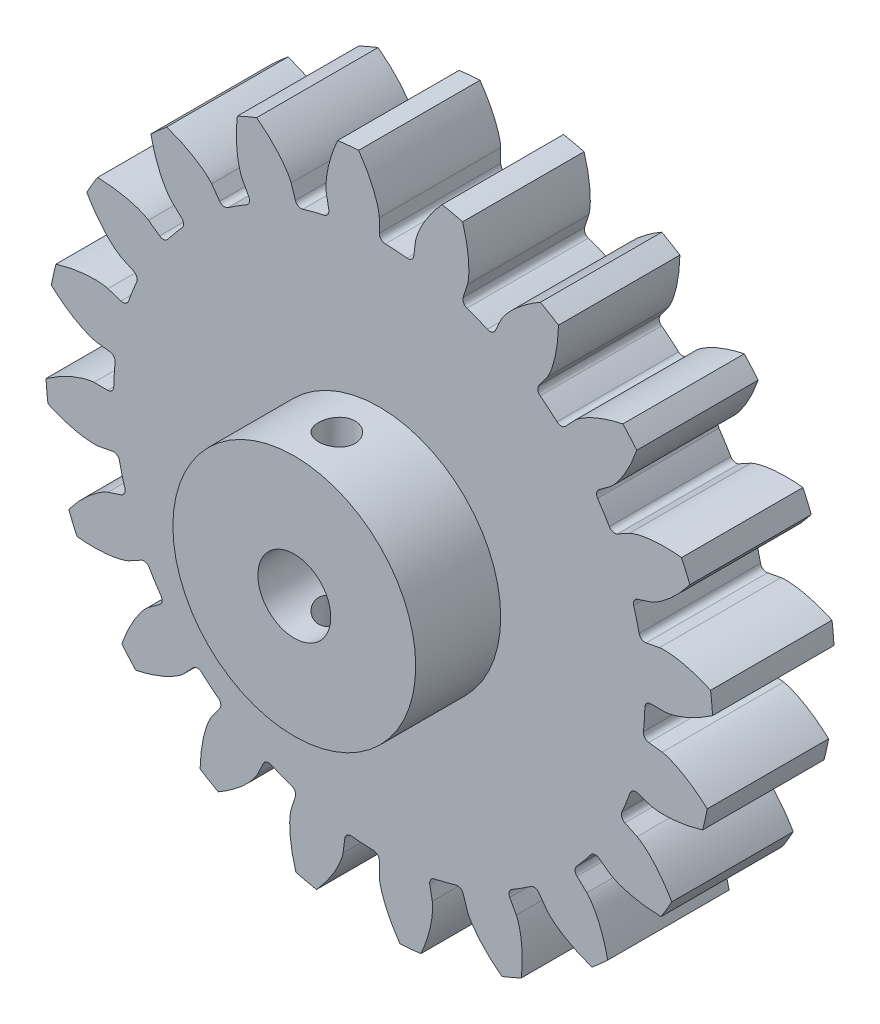
SolidWorks part; units mm, degrees
note: '?' marks a value the reader was unsure of.
material "Nylon 101"
ref_plane "Front Plane" through (0, 0, 0) normal (0, 0, 1) x (1, 0, 0)
ref_plane "Top Plane" through (0, 0, 0) normal (0, 1, 0) x (1, 0, 0)
ref_plane "Right Plane" through (0, 0, 0) normal (1, 0, 0) x (0, 0, -1)
sketch "Sketch1" plane through (0, 0, 0) normal (0, 0, 1) x (1, 0, 0)
  circle A0 centre (0, 0) radius 27.5
  dimension "D1" = 55
extrude "Boss-Extrude1" add sketch "Sketch1" along normal blind 10
sketch "Sketch2" plane through (0, 0, 10) normal (0, 0, 1) x (1, 0, 0)
  line L0 (22.3694, 0) -> (23.4923, 0)
  line L1 (0, 0) -> (27.4443, -1.7488) construction
  line L2 (22.1885, -2.8393) -> (23.3023, -2.9818)
  circle A0 centre (0, 0) radius 25 construction
  circle A1 centre (0, 0) radius 23.4923 construction
  arc A2 (21.7547, -2.291) -> (21.8695, -0.4888) centre (0, 0) ccw
  circle A3 centre (0, 0) radius 27.5 construction
  arc A4 (22.1885, -2.8393) -> (21.7547, -2.291) centre (22.252, -2.3433) cw
  arc A5 (21.8695, -0.4888) -> (22.3694, 0) centre (22.3694, -0.5) cw
  spline S0 degree 4 poles (23.4923, 0) (23.5003, 0.0001) (23.5229, 0.0008) (23.5654, 0.0035) (23.6347, 0.0099) (23.7229, 0.021) (23.8366, 0.0388) (23.9701, 0.064) (24.1163, 0.0963) (24.2747, 0.1362) (24.4321, 0.1804) (24.5885, 0.2284) (24.7436, 0.2799) (24.9307, 0.3464) (25.1538, 0.4321) (25.4127, 0.5406) (25.7039, 0.6737) (25.998, 0.82) (26.2849, 0.9725) (26.5718, 1.1365) (26.8473, 1.3021) (27.1301, 1.484) (27.3894, 1.6571) (27.6761, 1.8618) (27.9062, 2.0302) (28.2054, 2.2638) (28.3807, 2.4052) (28.5843, 2.5745) (28.6738, 2.6518) (28.729, 2.6993) knots 0 0 0 0 0 0.005377 0.015084 0.028532 0.04661 0.064855 0.092111 0.119476 0.146842 0.174209 0.201575 0.228941 0.256307 0.307035 0.361767 0.4165 0.471232 0.525964 0.580697 0.635429 0.690161 0.744894 0.799626 0.854358 0.909091 0.954545 1 1 1 1 1 construction
  spline S1 degree 4 poles (23.4923, 0) (23.5003, 0.0001) (23.5229, 0.0008) (23.5654, 0.0035) (23.6347, 0.0099) (23.7229, 0.021) (23.8366, 0.0388) (23.9701, 0.064) (24.1163, 0.0963) (24.2747, 0.1362) (24.4321, 0.1804) (24.5885, 0.2284) (24.7436, 0.2799) (24.9307, 0.3464) (25.1538, 0.4321) (25.4127, 0.5406) (25.7039, 0.6737) (25.998, 0.82) (26.2849, 0.9725) (26.5718, 1.1365) (26.8473, 1.3021) (27.1301, 1.484) (27.3894, 1.6571) (27.6761, 1.8618) (27.9062, 2.0302) (28.1405, 2.2132) (28.254, 2.3035) (28.3118, 2.3503) knots 0 0 0 0 0 0.005377 0.015084 0.028532 0.04661 0.064855 0.092111 0.119476 0.146842 0.174209 0.201575 0.228941 0.256307 0.307035 0.361767 0.4165 0.471232 0.525964 0.580697 0.635429 0.690161 0.744894 0.799626 0.854358 0.909091 0.909091 0.909091 0.909091 0.909091
  spline S2 degree 4 poles (23.3023, -2.9818) (23.3103, -2.983) (23.3325, -2.9865) (23.3744, -2.9946) (23.4423, -3.0097) (23.5284, -3.0319) (23.6389, -3.064) (23.7681, -3.106) (23.909, -3.1565) (24.0611, -3.2163) (24.2116, -3.2801) (24.3606, -3.3476) (24.5079, -3.4183) (24.6851, -3.508) (24.8955, -3.6213) (25.1385, -3.7618) (25.4105, -3.9308) (25.6836, -4.1132) (25.9489, -4.3009) (26.2126, -4.5) (26.4649, -4.6992) (26.7223, -4.9156) (26.9576, -5.1201) (27.2159, -5.3596) (27.4228, -5.5559) (27.6899, -5.8255) (27.8459, -5.988) (28.0263, -6.1818) (28.1053, -6.2699) (28.154, -6.324) knots 0 0 0 0 0 0.005377 0.015084 0.028532 0.04661 0.064855 0.092111 0.119476 0.146842 0.174209 0.201575 0.228941 0.256307 0.307035 0.361767 0.4165 0.471232 0.525964 0.580697 0.635429 0.690161 0.744894 0.799626 0.854358 0.909091 0.954545 1 1 1 1 1 construction
  spline S3 degree 4 poles (23.3023, -2.9818) (23.3103, -2.983) (23.3325, -2.9865) (23.3744, -2.9946) (23.4423, -3.0097) (23.5284, -3.0319) (23.6389, -3.064) (23.7681, -3.106) (23.909, -3.1565) (24.0611, -3.2163) (24.2116, -3.2801) (24.3606, -3.3476) (24.5079, -3.4183) (24.6851, -3.508) (24.8955, -3.6213) (25.1385, -3.7618) (25.4105, -3.9308) (25.6836, -4.1132) (25.9489, -4.3009) (26.2126, -4.5) (26.4649, -4.6992) (26.7223, -4.9156) (26.9576, -5.1201) (27.2159, -5.3596) (27.4228, -5.5559) (27.632, -5.7671) (27.7331, -5.8711) (27.7845, -5.9248) knots 0 0 0 0 0 0.005377 0.015084 0.028532 0.04661 0.064855 0.092111 0.119476 0.146842 0.174209 0.201575 0.228941 0.256307 0.307035 0.361767 0.4165 0.471232 0.525964 0.580697 0.635429 0.690161 0.744894 0.799626 0.854358 0.909091 0.909091 0.909091 0.909091 0.909091
  dimension "D1" = 50
  dimension "D2" = 46.9846
  dimension "D3" = 43.75
  dimension "D6" = 0.5
  dimension "D4" = 3.646
  dimension "D5" = 3.646
extrude "Cut-Extrude1" cut sketch "Sketch2" against normal through all and the other way through all
ref_axis "Axis2" through (0, 0, 10) along (0, 0, -1)?
pattern_circular "CirPattern6" count 20 over 360 about axis through (0, 0, 10) along (0, 0, -1) of "Cut-Extrude1"
sketch "Sketch3" plane through (0, 0, 10) normal (0, 0, 1) x (1, 0, 0)
  circle A0 centre (0, 0) radius 3
  circle A5 centre (0, 0) radius 7 construction
  dimension "D1" = 6
  dimension "D2" = 14
extrude "Cut-Extrude2" cut sketch "Sketch3" against normal blind 10
sketch "Sketch4" plane through (0, 0, 10) normal (0, 0, 1) x (1, 0, 0)
  circle A0 centre (0, 0) radius 3
  circle A1 centre (0, 0) radius 10
  circle A2 centre (0, 0) radius 3 construction
  dimension "D1" = 20
extrude "Boss-Extrude2" add sketch "Sketch4" along normal blind 7
ref_plane "Plane1" through (0, 0, 5) normal (0, 0, 1) x (1, 0, 0)
sketch "Sketch5" plane through (0, 0, 0) normal (0, 1, 0) x (1, 0, 0)
  line L0 (0, -10) -> (0, 0) construction
  line L1 (-23.4923, -10) -> (23.4923, -10) construction
  circle A0 centre (0, -13.5) radius 1.5
  dimension "D1" = 3
  dimension "D2" = 3.5
extrude "Cut-Extrude3" cut sketch "Sketch5" against normal through all and the other way through all
mirror "Mirror2" about plane through (0, 0, 5) normal (0, 0, 1) of "Boss-Extrude2", "Cut-Extrude3"
equation "\"m\"= 2.5'module"
equation "\"p\"= 1 / \"m\"'Diametral pitch"
equation "\"N\"= 20'Number of teeth"
equation "\"phi\"= 20'pressure angle"
equation "\"a\"= \"m\"'addendum"
equation "\"b\"= 1.25 * \"m\"'deddendum"
equation "\"c\"= \"b\" - \"a\"'clearance"
equation "\"dp\"= \"N\" * \"m\"'pitch circle diameter"
equation "\"db\"= \"dp\" * cos ( \"phi\" )'base circle diameter"
equation "\"D1@Sketch1\" = \"dp\" + 2 * \"a\"'Addendum circle dia "
equation "\"D1@Sketch2\" = \"dp\"'pitch circle dia "
equation "\"D2@Sketch2\"= \"db\" 'base circle dia"
equation "\"D3@Sketch2\"= \"dp\" - 2 * \"b\" 'deddendum circle dia"
equation "\"alpha\"= sqr ( \"dp\" ^ 2 - \"db\" ^ 2 ) / \"db\" * 180 / pi - \"phi\""
equation "\"D4@Sketch2\" = 360 / ( 4 * \"N\" ) - \"alpha\""
equation "\"D5@Sketch2\" = \"D4@Sketch2\""
equation "\"D6@Sketch2\" = 0.8 * \"c\""
